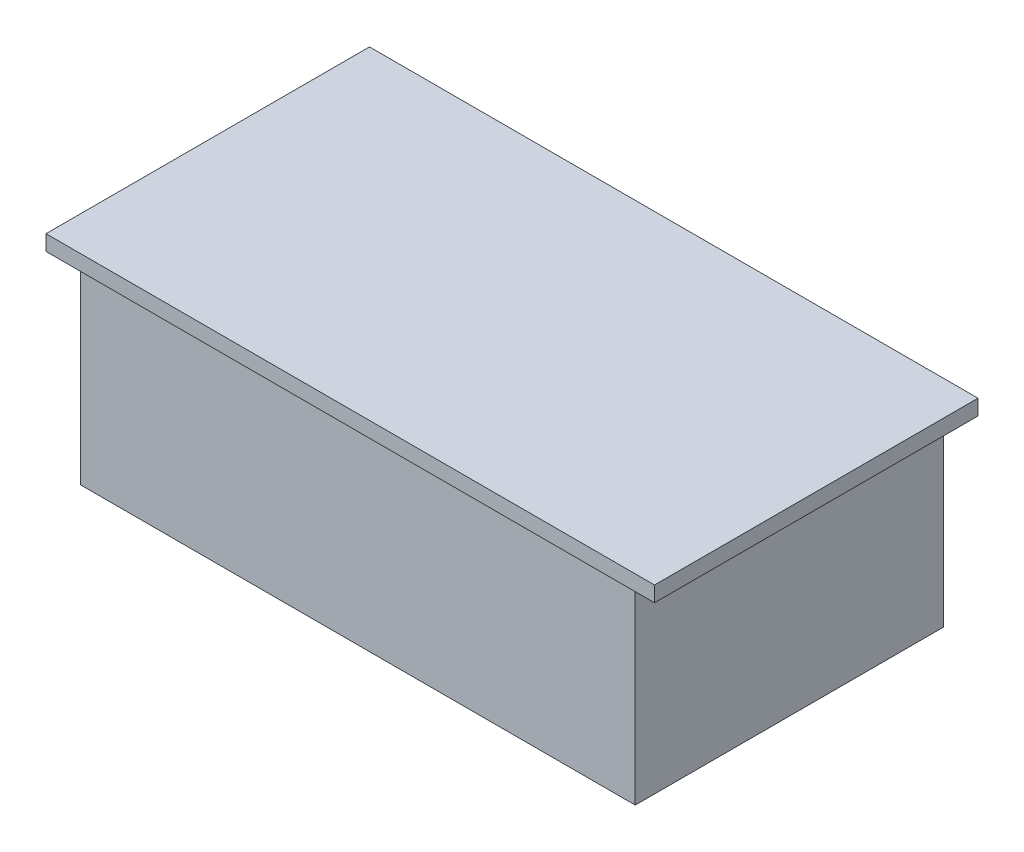
SolidWorks part; units mm, degrees
ref_plane "Front Plane" through (0, 0, 0) normal (0, 0, 1) x (1, 0, 0)
ref_plane "Top Plane" through (0, 0, 0) normal (0, 1, 0) x (1, 0, 0)
ref_plane "Right Plane" through (0, 0, 0) normal (1, 0, 0) x (0, 0, -1)
sketch "草图1" plane through (0, 0, 0) normal (0, 1, 0) x (1, 0, 0)
  line L1 (-36, -20) -> (36, -20)
  line L2 (-36, -20) -> (-36, 20)
  line L3 (-36, 20) -> (36, 20)
  line L4 (36, -20) -> (36, 20)
  line L5 (-36, -20) -> (36, 20) construction
  line L6 (-36, 20) -> (36, -20) construction
  line L7 (-39.5, -21) -> (39.5, -21)
  line L8 (-39.5, -21) -> (-39.5, 21)
  line L9 (-39.5, 21) -> (39.5, 21)
  line L10 (39.5, -21) -> (39.5, 21)
  line L11 (-39.5, -21) -> (39.5, 21) construction
  line L12 (-39.5, 21) -> (39.5, -21) construction
  point P0 (0, 0)
  point P6 (0, 0)
  dimension "D1" = 72
  dimension "D2" = 40
  dimension "D3" = 79
  dimension "D4" = 42
extrude "凸台-拉伸1" add sketch "草图1" along normal blind 25 contours L4 L3 L2 L1
extrude "凸台-拉伸3" add sketch "草图1<4>" along normal blind 2 from surface separate body contours L10 L9 L8 L7 starting at face at (0, 25, 0)
sketch "草图1<4>" plane through (0, 0, 0) normal (0, 1, 0) x (1, 0, 0) same geometry as "草图1"
